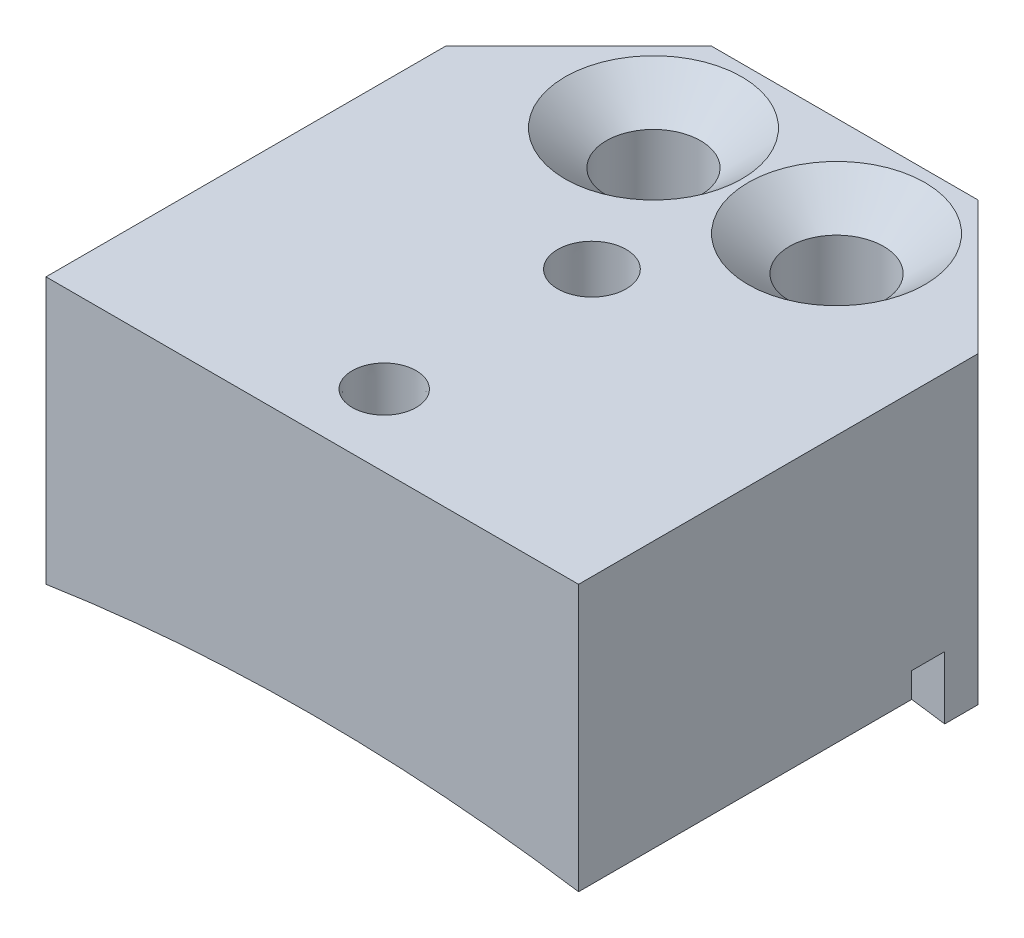
SolidWorks part; units mm, degrees
ref_plane "Front Plane" through (0, 0, 0) normal (0, 0, 1) x (1, 0, 0)
ref_plane "Top Plane" through (0, 0, 0) normal (0, 1, 0) x (1, 0, 0)
ref_plane "Right Plane" through (0, 0, 0) normal (1, 0, 0) x (0, 0, -1)
sketch "Sketch1" plane through (0, 0, 0) normal (0, 1, 0) x (1, 0, 0)
  line L0 (-28.5118, 6.4953) -> (-22.1618, 12.8453)
  line L1 (-22.1618, 12.8453) -> (-9.4618, 12.8453)
  line L2 (-28.5118, 6.4953) -> (-28.5118, -12.5547)
  line L3 (-28.5118, -12.5547) -> (-3.1118, -12.5547)
  line L4 (-3.1118, 6.4953) -> (-3.1118, -12.5547)
  line L5 (-9.4618, 12.8453) -> (-3.1118, 6.4953)
  line L6 (-15.8118, -12.5547) -> (-15.8118, 12.8453) construction
  line L8 (-3.1118, 6.4953) -> (-3.1118, 12.8453) construction
  line L9 (-3.1118, 12.8453) -> (-9.4618, 12.8453) construction
  dimension "D1" = 12.7
  dimension "D2" = 25.4
  dimension "D3" = 25.4
extrude "Boss-Extrude1" add sketch "Sketch1" along normal blind 12.7
sketch "Sketch2" plane through (0, 0, 12.5547) normal (0, 0, 1) x (1, 0, 0)
  circle A0 centre (-15.8118, -82.8523) radius 83.82
  dimension "D1" = 167.64
extrude "Cut-Extrude1" cut sketch "Sketch2" against normal through all both and the other way through all
sketch "Sketch5" plane through (0, 0, -12.8453) normal (0, 0, -1) x (-1, 0, 0)
  line L0 (3.1118, 12.7) -> (3.1118, 0) construction
  line L1 (3.1118, 12.7) -> (3.1118, 0)
  line L4 (28.5118, 12.7) -> (28.5118, 0) construction
  line L5 (28.5118, 12.7) -> (28.5118, 0)
  line L6 (28.5118, -1.7992) -> (28.5118, 0)
  line L7 (3.1118, -1.7992) -> (3.1118, 0)
  line L8 (3.1118, 12.7) -> (28.5118, 12.7)
  arc A0 (3.1118, -1.7992) -> (28.5118, -1.7992) centre (15.8118, -82.8523) cw
  arc A1 (28.5118, 0) -> (3.1118, 0) centre (15.8118, -82.8523) ccw construction
  arc A2 (28.5118, 0) -> (3.1118, 0) centre (15.8118, -82.8523) ccw construction
  dimension "D1" = 82.042
extrude "Boss-Extrude2" add sketch "Sketch5" against normal blind 7.9375
chamfer "Chamfer1" distance 6.35 angle 45 2 edges at (-28.5118, 5.4504, -12.8453) (-3.1118, 5.4504, -12.8453)
hole_wizard "CSK for #8 Flat Head Machine Screw (100)1" positions "Sketch3" profile "Sketch4" countersink size "#8" standard "ANSI Inch" end condition through all
sketch "Sketch3" plane through (0, 12.7, 0) normal (0, 1, 0) x (1, 0, 0)
  line L0 (-15.8118, 12.8453) -> (-15.8118, 3.4006) construction
  line L1 (-9.4618, 12.8453) -> (-22.1618, 12.8453) construction
  point P0 (-20.1775, 8.0828)
  point P12 (-11.4462, 8.0828)
  dimension "D1" = 4.7625
  dimension "D2" = 4.3656
sketch "Sketch4" plane through (-20.1775, 12.7, -8.0828) normal (1, 0, 0) x (0, 0, 1)
  line L0 (0, 0) -> (0, 14.4992)
  line L1 (0, 14.4992) -> (2.2479, 14.4992)
  line L2 (2.2479, 14.4992) -> (2.2479, 1.6518)
  line L3 (2.2479, 1.6518) -> (4.2164, 0)
  line L5 (4.2164, 0) -> (0, 0)
  line L6 (-2.2479, 1.6518) -> (-4.2164, 0) construction
  line L11 (0, -6.35) -> (0, 107.95) construction
  dimension "Thru Hole Dia." = 4.4958
  dimension "Thru Hole Depth" = 14.4992
  dimension "Near C'Sink Dia." = 8.4328
  dimension "Near C'Sink Angle" = 100
sketch "Sketch6" plane through (0, 12.7, 0) normal (0, 1, 0) x (1, 0, 0)
  spline S0 degree 3 poles (-15.9109, -10.6497) (-15.6088, -10.6497) (-15.4088, -10.6093) (-15.0421, -10.4569) (-14.8723, -10.3433) (-14.6614, -10.1321) (-14.5971, -10.0536) (-14.4867, -9.888) (-14.44, -9.8004) (-14.3254, -9.523) (-14.286, -9.3252) (-14.2863, -9.0237) (-14.2962, -8.9248) (-14.3351, -8.7299) (-14.3646, -8.633) (-14.4412, -8.4488) (-14.488, -8.3613) (-14.5989, -8.1955) (-14.6633, -8.1172) (-14.8743, -7.9067) (-15.0444, -7.7932) (-15.4113, -7.6415) (-15.6118, -7.6017) (-15.9102, -7.6018) (-16.0112, -7.6118) (-16.2064, -7.6508) (-16.3014, -7.6796) (-16.5784, -7.7944) (-16.7462, -7.9063) (-16.9595, -8.1198) (-17.0224, -8.1968) (-17.1327, -8.362) (-17.1804, -8.4512) (-17.2567, -8.6357) (-17.2855, -8.7307) (-17.3244, -8.9262) (-17.3342, -9.0271) (-17.3341, -9.3253) (-17.2941, -9.5259) (-17.142, -9.8926) (-17.0285, -10.0627) (-16.8176, -10.2736) (-16.7392, -10.3379) (-16.5735, -10.4485) (-16.486, -10.4953) (-16.3014, -10.5718) (-16.2047, -10.6011) (-16.0099, -10.6398) (-15.9109, -10.6497) (-15.6088, -10.6497) (-15.4088, -10.6093) knots -0.03125 -0.03125 0 0 0.0625 0.0625 0.125 0.125 0.15625 0.15625 0.1875 0.1875 0.25 0.25 0.28125 0.28125 0.3125 0.3125 0.34375 0.34375 0.375 0.375 0.4375 0.4375 0.5 0.5 0.53125 0.53125 0.5625 0.5625 0.625 0.625 0.65625 0.65625 0.6875 0.6875 0.71875 0.71875 0.75 0.75 0.8125 0.8125 0.875 0.875 0.90625 0.90625 0.9375 0.9375 0.96875 0.96875 1 1 1.0625 1.0625 1.125 only from (-15.8102, -10.6497) to (-15.8102, -10.6497) construction
  spline S1 degree 3 poles (-15.9109, -10.6497) (-15.6088, -10.6497) (-15.4088, -10.6093) (-15.0421, -10.4569) (-14.8723, -10.3433) (-14.6614, -10.1321) (-14.5971, -10.0536) (-14.4867, -9.888) (-14.44, -9.8004) (-14.3254, -9.523) (-14.286, -9.3252) (-14.2863, -9.0237) (-14.2962, -8.9248) (-14.3351, -8.7299) (-14.3646, -8.633) (-14.4412, -8.4488) (-14.488, -8.3613) (-14.5989, -8.1955) (-14.6633, -8.1172) (-14.8743, -7.9067) (-15.0444, -7.7932) (-15.4113, -7.6415) (-15.6118, -7.6017) (-15.9102, -7.6018) (-16.0112, -7.6118) (-16.2064, -7.6508) (-16.3014, -7.6796) (-16.5784, -7.7944) (-16.7462, -7.9063) (-16.9595, -8.1198) (-17.0224, -8.1968) (-17.1327, -8.362) (-17.1804, -8.4512) (-17.2567, -8.6357) (-17.2855, -8.7307) (-17.3244, -8.9262) (-17.3342, -9.0271) (-17.3341, -9.3253) (-17.2941, -9.5259) (-17.142, -9.8926) (-17.0285, -10.0627) (-16.8176, -10.2736) (-16.7392, -10.3379) (-16.5735, -10.4485) (-16.486, -10.4953) (-16.3014, -10.5718) (-16.2047, -10.6011) (-16.0099, -10.6398) (-15.9109, -10.6497) (-15.6088, -10.6497) (-15.4088, -10.6093) knots -0.03125 -0.03125 0 0 0.0625 0.0625 0.125 0.125 0.15625 0.15625 0.1875 0.1875 0.25 0.25 0.28125 0.28125 0.3125 0.3125 0.34375 0.34375 0.375 0.375 0.4375 0.4375 0.5 0.5 0.53125 0.53125 0.5625 0.5625 0.625 0.625 0.65625 0.65625 0.6875 0.6875 0.71875 0.71875 0.75 0.75 0.8125 0.8125 0.875 0.875 0.90625 0.90625 0.9375 0.9375 0.96875 0.96875 1 1 1.0625 1.0625 1.125 only from (-15.8102, -10.6497) to (-15.8102, -10.6497)
  spline S2 degree 3 poles (-17.442, 0.8881) (-17.442, 0.5646) (-17.3987, 0.3504) (-17.2355, -0.0422) (-17.1139, -0.2241) (-16.8877, -0.4499) (-16.8036, -0.5187) (-16.6263, -0.6369) (-16.5325, -0.687) (-16.2355, -0.8097) (-16.0236, -0.8519) (-15.7008, -0.8516) (-15.5949, -0.8409) (-15.3862, -0.7993) (-15.2825, -0.7677) (-15.0851, -0.6857) (-14.9915, -0.6355) (-14.814, -0.5168) (-14.7301, -0.4479) (-14.5047, -0.222) (-14.3832, -0.0397) (-14.2207, 0.3532) (-14.178, 0.5678) (-14.1782, 0.8874) (-14.1889, 0.9955) (-14.2306, 1.2046) (-14.2615, 1.3063) (-14.3435, 1.5041) (-14.3946, 1.5994) (-14.5128, 1.7761) (-14.5805, 1.8587) (-14.7329, 2.0109) (-14.8153, 2.0784) (-14.9922, 2.1965) (-15.0878, 2.2476) (-15.2854, 2.3293) (-15.3871, 2.3601) (-15.5964, 2.4017) (-15.7045, 2.4123) (-16.0238, 2.4121) (-16.2385, 2.3692) (-16.6313, 2.2065) (-16.8134, 2.0849) (-17.0392, 1.8591) (-17.1081, 1.7751) (-17.2266, 1.5977) (-17.2767, 1.5039) (-17.3586, 1.3063) (-17.39, 1.2027) (-17.4314, 0.9941) (-17.442, 0.8881) (-17.442, 0.5646) (-17.3987, 0.3504) knots -0.03125 -0.03125 0 0 0.0625 0.0625 0.125 0.125 0.15625 0.15625 0.1875 0.1875 0.25 0.25 0.28125 0.28125 0.3125 0.3125 0.34375 0.34375 0.375 0.375 0.4375 0.4375 0.5 0.5 0.53125 0.53125 0.5625 0.5625 0.59375 0.59375 0.625 0.625 0.65625 0.65625 0.6875 0.6875 0.71875 0.71875 0.75 0.75 0.8125 0.8125 0.875 0.875 0.90625 0.90625 0.9375 0.9375 0.96875 0.96875 1 1 1.0625 1.0625 1.125 only from (-17.442, 0.7803) to (-17.442, 0.7803) construction
  spline S3 degree 3 poles (-17.442, 0.8881) (-17.442, 0.5646) (-17.3987, 0.3504) (-17.2355, -0.0422) (-17.1139, -0.2241) (-16.8877, -0.4499) (-16.8036, -0.5187) (-16.6263, -0.6369) (-16.5325, -0.687) (-16.2355, -0.8097) (-16.0236, -0.8519) (-15.7008, -0.8516) (-15.5949, -0.8409) (-15.3862, -0.7993) (-15.2825, -0.7677) (-15.0851, -0.6857) (-14.9915, -0.6355) (-14.814, -0.5168) (-14.7301, -0.4479) (-14.5047, -0.222) (-14.3832, -0.0397) (-14.2207, 0.3532) (-14.178, 0.5678) (-14.1782, 0.8874) (-14.1889, 0.9955) (-14.2306, 1.2046) (-14.2615, 1.3063) (-14.3435, 1.5041) (-14.3946, 1.5994) (-14.5128, 1.7761) (-14.5805, 1.8587) (-14.7329, 2.0109) (-14.8153, 2.0784) (-14.9922, 2.1965) (-15.0878, 2.2476) (-15.2854, 2.3293) (-15.3871, 2.3601) (-15.5964, 2.4017) (-15.7045, 2.4123) (-16.0238, 2.4121) (-16.2385, 2.3692) (-16.6313, 2.2065) (-16.8134, 2.0849) (-17.0392, 1.8591) (-17.1081, 1.7751) (-17.2266, 1.5977) (-17.2767, 1.5039) (-17.3586, 1.3063) (-17.39, 1.2027) (-17.4314, 0.9941) (-17.442, 0.8881) (-17.442, 0.5646) (-17.3987, 0.3504) knots -0.03125 -0.03125 0 0 0.0625 0.0625 0.125 0.125 0.15625 0.15625 0.1875 0.1875 0.25 0.25 0.28125 0.28125 0.3125 0.3125 0.34375 0.34375 0.375 0.375 0.4375 0.4375 0.5 0.5 0.53125 0.53125 0.5625 0.5625 0.59375 0.59375 0.625 0.625 0.65625 0.65625 0.6875 0.6875 0.71875 0.71875 0.75 0.75 0.8125 0.8125 0.875 0.875 0.90625 0.90625 0.9375 0.9375 0.96875 0.96875 1 1 1.0625 1.0625 1.125 only from (-17.442, 0.7803) to (-17.442, 0.7803)
extrude "Cut-Extrude2" cut sketch "Sketch6" against normal through all
sketch "Sketch7" plane through (-28.5118, 0, 0) normal (-1, 0, 0) x (0, 0, 1)
  line L1 (-4.9078, 0) -> (-3.3203, 0)
  line L2 (-4.9078, 0) -> (-4.9078, 1.1906)
  line L3 (-4.9078, 1.1906) -> (-3.3203, 1.1906)
  line L4 (-3.3203, 0) -> (-3.3203, 1.1906)
  dimension "D1" = 1.5875
  dimension "D2" = 1.1906
extrude "Cut-Extrude3" cut sketch "Sketch7" against normal through all
